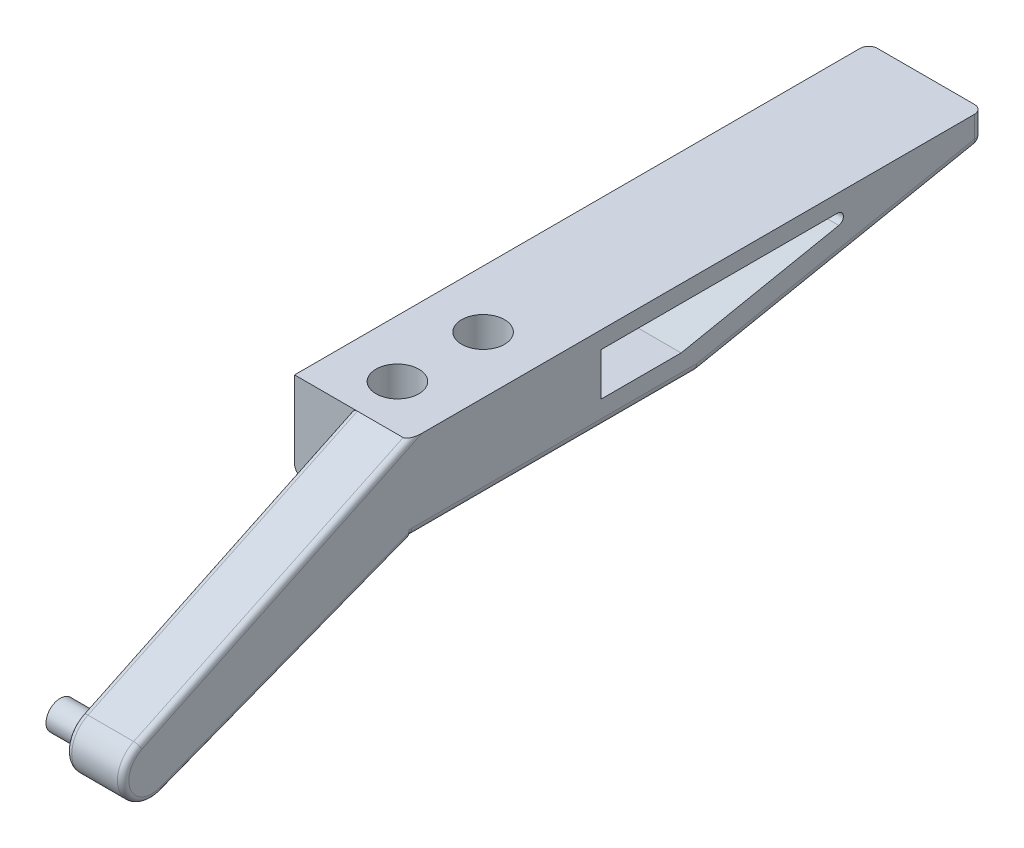
SolidWorks part; units mm, degrees
ref_plane "Front Plane" through (0, 0, 0) normal (0, 0, 1) x (1, 0, 0)
ref_plane "Top Plane" through (0, 0, 0) normal (0, 1, 0) x (1, 0, 0)
ref_plane "Right Plane" through (0, 0, 0) normal (1, 0, 0) x (0, 0, -1)
sketch "Sketch1" plane through (0, 0, 0) normal (0, 1, 0) x (1, 0, 0)
  line L1 (-20, 75) -> (20, 75)
  line L3 (-20, -75) -> (20, -75)
  line L4 (20, -75) -> (20, 75)
  line L5 (-20, -75) -> (-20, 75)
  circle A0 centre (0, -61.1649) radius 7.5
  circle A1 centre (0, -31.1649) radius 7.5
extrude "Boss-Extrude1" add sketch "Sketch1" against normal blind 30 contours L5 L1 L4 L3
sketch "Sketch3" plane through (0, 0, 0) normal (0, 1, 0) x (1, 0, 0)
  circle A0 centre (0, -60) radius 7.5
  circle A1 centre (0, -30) radius 7.5
extrude "Cut-Extrude1" cut sketch "Sketch3" against normal blind 30 contours A0 | A1
sketch "Sketch4" plane through (-20, 0, 0) normal (-1, 0, 0) x (0, 0, 1)
  line L1 (-75, -30) -> (-75, 0) construction
  line L2 (-75, -8) -> (0, -30)
  line L3 (75, -30) -> (-75, -30) construction
  line L4 (0, -30) -> (-75, -30)
  line L5 (-75, -30) -> (-75, -8)
extrude "Cut-Extrude2" cut sketch "Sketch4" against normal blind 49
sketch "Sketch6" plane through (0, 0, -75) normal (0, 0, -1) x (-1, 0, 0)
  line L1 (-20, 0) -> (20, 0)
  line L2 (-20, 0) -> (-20, -30)
  line L3 (-20, -30) -> (20, -30)
  line L4 (20, 0) -> (20, -30)
extrude "Boss-Extrude2" add sketch "Sketch6" along normal blind 50 and the other way blind 87
sketch "Sketch7" plane through (-20, 0, 0) normal (-1, 0, 0) x (0, 0, 1)
  line L1 (-125, -30) -> (-125, 0) construction
  line L2 (-125, -10) -> (-25, -30)
  line L3 (75, -30) -> (-125, -30) construction
  line L4 (-25, -30) -> (-125, -30)
  line L5 (-125, -30) -> (-125, -10)
extrude "Cut-Extrude3" cut sketch "Sketch7" against normal blind 50
sketch "Sketch8" plane through (0, 0, 75) normal (0, 0, 1) x (1, 0, 0)
  line L10 (20, -30) -> (6, -30)
  line L11 (-20, -30) -> (20, -30) construction
  line L12 (6, -30) -> (6, 0)
  line L13 (-20, 0) -> (20, 0) construction
  line L14 (6, 0) -> (20, 0)
  line L15 (20, 0) -> (20, -30)
  line L16 (-20, -30) -> (-6, -30)
  line L17 (-6, -30) -> (-6, 0)
  line L18 (-6, 0) -> (-20, 0)
  line L19 (-20, -30) -> (-20, 0) construction
  line L20 (-20, 0) -> (-20, -30)
extrude "Boss-Extrude4" add sketch "Sketch8" along normal blind 50
sketch "Sketch11" plane through (0, 0, 0) normal (0, 1, 0) x (1, 0, 0)
  line L0 (6, -75) -> (20, -75)
  line L1 (20, -125) -> (20, 125) construction
  line L2 (20, -75) -> (20, -125)
  line L3 (20, -125) -> (6, -125)
  line L4 (6, -125) -> (6, -75)
  line L5 (-6, -75) -> (-6, -125)
  line L6 (-6, -125) -> (-20, -125)
  line L7 (-20, -125) -> (-20, -75)
  line L8 (-20, -125) -> (-20, 125) construction
  line L9 (-20, -75) -> (-6, -75)
extrude "Cut-Extrude4" cut sketch "Sketch11" against normal blind 15
sketch "Sketch12" plane through (0, 0, 125) normal (0, 0, 1) x (1, 0, 0)
  line L1 (-20, -15) -> (-6, -15)
  line L2 (-20, -15) -> (-20, -30)
  line L3 (-20, -30) -> (-6, -30)
  line L4 (-6, -15) -> (-6, -30)
  line L5 (6, -15) -> (20, -15)
  line L6 (6, -15) -> (6, -30)
  line L7 (6, -30) -> (20, -30)
  line L8 (20, -15) -> (20, -30)
extrude "Boss-Extrude5" add sketch "Sketch12" along normal blind 10
sketch "Sketch13" plane through (-6, 0, 0) normal (1, 0, 0) x (0, 0, -1)
  circle A0 centre (-125, -22.5) radius 5
extrude "Boss-Extrude6" add sketch "Sketch13" along normal up to surface (12 mm away) contours A0 up to face at (6, -22.5, 105)
sketch "Sketch14" plane through (0, -30, 0) normal (0, -1, 0) x (1, 0, 0)
  circle A0 centre (0, 60) radius 7.5
  circle A1 centre (0, 60) radius 6
  circle A2 centre (0, 30) radius 6
  circle A3 centre (0, 30) radius 7.5
extrude "Boss-Extrude7" add sketch "Sketch14" against normal blind 5
sketch "Sketch15" plane through (20, 0, 0) normal (1, 0, 0) x (0, 0, -1)
  line L0 (125, 0) -> (105, 0)
  line L1 (-75, 0) -> (125, 0) construction
  circle A0 centre (52.5, 373.9316) radius 377.5991
extrude "Cut-Extrude5" cut sketch "Sketch15" against normal blind 50 contours A0
fillet "Fillet1" radius 3 2 edges at (20, -30, 55) (-20, -30, 55)
fillet "Fillet2" radius 3 8 edges at (-20, -18.5, -82.5) (-19.1213, -29.1213, -29.3934) (0, -30, -25) (19.1213, -29.1213, -29.3934) (-20, -5, -125) (20, -5, -125) (0, -10, -125) (20, -18.5, -82.5)
sketch "Sketch17" plane through (0, 0, 75) normal (0, 0, 1) x (1, 0, 0)
  line L0 (20, 0) -> (20, -30)
  line L1 (14.0365, -30) -> (20, -30)
  line L2 (6, -30) -> (17, -30) construction
  line L3 (20, 0) -> (-20, 0)
  line L4 (-20, 0) -> (-20, -30)
  line L5 (-20, -30) -> (14.0365, -30)
extrude "Boss-Extrude11" add sketch "Sketch17" along normal up to surface (60 mm away) up to face at (13.9243, -23.5243, 135)
sketch "Sketch23" plane through (0, 0, 135) normal (0, 0, 1) x (1, 0, 0)
  line L0 (-20, -15) -> (0, -15)
  line L1 (-20, 0) -> (-20, -30) construction
  line L3 (0, -30) -> (0, -15)
  line L4 (-20, -30) -> (20, -30) construction
  line L6 (-20, -30) -> (0, -30)
  line L7 (-20, -15) -> (-20, -30)
  line L9 (-20, -30) -> (20, -30)
  line L10 (-20, -30) -> (-20, 0)
  line L11 (-20, 0) -> (20, 0)
  line L12 (20, -30) -> (20, 0)
  line M1 (-20, 0) -> (-20, -30)
  line M2 (-20, -30) -> (20, -30)
  line M3 (20, -30) -> (20, 0)
  line M4 (20, 0) -> (-20, 0)
extrude "Cut-Extrude8" cut sketch "Sketch23" against normal up to surface (60 mm away) contours L3 L0 M2 M3 M4 M1 region at (3.3333, -12.5, 135) up to face at (19.2071, -29.2071, 75)
sketch "Sketch25" plane through (0, 0, 75) normal (0, 0, 1) x (1, 0, 0)
  line L0 (-20, -15) -> (-20, 0)
  line L1 (-20, 0) -> (0, 0)
  line L2 (-20, 0) -> (20, 0) construction
  line L3 (0, 0) -> (0, -15)
  line L4 (0, -15) -> (-20, -15)
extrude "Boss-Extrude13" add sketch "Sketch25" along normal up to surface (60 mm away) up to face at (-10, -22.5, 135)
sketch "Sketch26" plane through (0, 0, 0) normal (1, 0, 0) x (0, 0, -1)
  circle A0 centre (-125, -15) radius 5
extrude "Boss-Extrude14" add sketch "Sketch26" along normal up to surface (20 mm away) up to face at (20, -9.3154, -31.9576)
sketch "Sketch27" plane through (0, 0, 75) normal (0, 0, 1) x (1, 0, 0)
  line L1 (20, 0) -> (-20, 0)
  line L2 (20, 0) -> (20, -60)
  line L3 (20, -60) -> (-20, -60)
  line L4 (-20, 0) -> (-20, -60)
extrude "Boss-Extrude15" add sketch "Sketch27" along normal up to surface (60 mm away) up to face at (-10, -15, 135)
sketch "Sketch28" plane through (0, 0, 75) normal (0, 0, -1) x (-1, 0, 0)
  line L0 (20, -27) -> (20, -60) construction
  line L1 (-20, -60) -> (20, -60)
  line L2 (-20, -60) -> (-20, -30)
  line L3 (-20, -30) -> (20, -30)
  line L4 (20, -60) -> (20, -30)
extrude "Cut-Extrude9" cut sketch "Sketch28" against normal blind 1
sketch "Sketch29" plane through (0, 0, 135) normal (0, 0, 1) x (1, 0, 0)
  line L0 (20, 0) -> (-20, 0) construction
  line L1 (20, -60) -> (0, -60)
  line L2 (20, -60) -> (20, 0)
  line L3 (20, 0) -> (0, 0)
  line L4 (0, -60) -> (0, 0)
extrude "Cut-Extrude10" cut sketch "Sketch29" against normal up to surface (59 mm away) up to face at (0, -45, 76)
fillet "Fillet6" radius 3 1 edges at (-20, -30, 75.5)
fillet "Fillet7" radius 3 1 edges at (20, -30, 75.5)
sketch "Sketch30" plane through (0, 0, 135) normal (0, 0, 1) x (1, 0, 0)
  line L0 (-20, 0) -> (-20, -30)
  line L1 (-20, 0) -> (-20, -60) construction
  line L2 (-20, -15) -> (0, -15)
  line L3 (0, 0) -> (0, -60) construction
  line L4 (0, -15) -> (0, 0)
  line L5 (0, 0) -> (-20, 0)
  line M1 (0, -60) -> (0, 0)
  line M2 (0, 0) -> (-20, 0)
  line M3 (-20, 0) -> (-20, -60)
extrude "Cut-Extrude11" cut sketch "Sketch30" against normal up to surface (59 mm away) contours L2 M3 M1 M2 region at (-10, -7.5, 135) up to face at (11.5243, -17.5243, 76)
sketch "Sketch31" plane through (0, 0, 0) normal (1, 0, 0) x (0, 0, -1)
  line L0 (-129.7694, -41.2162) -> (-129.0122, -40.847)
  line L1 (-76, -15) -> (-76, -30)
  line L2 (-76, -30) -> (-118.7075, -57.7744)
  line L3 (-129.6113, -41.0081) -> (-129.7694, -41.2162)
  line L4 (-89.6197, -15) -> (-129.6113, -41.0081)
  line L5 (-76, -30) -> (-76, -60)
  line L6 (-76, -60) -> (-135, -60)
  line L7 (-135, -60) -> (-135, -15)
  line L8 (-135, -15) -> (-76, -15)
  line L9 (-96, -19.1494) -> (-129.6113, -41.0081) construction
  line L10 (-96, -15) -> (-96, -19.1494) construction
  circle A0 centre (-125.0122, -50.0122) radius 10
  line M9 (-76, -15) -> (-135, -15)
  line M10 (-135, -15) -> (-135, -60)
  line M11 (-135, -60) -> (-76, -60)
  line M12 (-76, -60) -> (-76, -30)
  dimension "D1" = 20
extrude "Cut-Extrude13" cut sketch "Sketch31" against normal blind 28 contours A0 M10 M11 | A0 L2 M11 M12 | A0 L3 L4 M9 M10 region at (0, -24.9817, 119.9741) region at (0, -57.7806, 132.7806) region at (0, -50.0084, 91.4032)
sketch "Sketch32" plane through (0, 0, 0) normal (1, 0, 0) x (0, 0, -1)
  line L0 (-76, -30) -> (-76, 0)
  line L1 (-76, 0) -> (-129.7694, -41.2162)
  line L2 (-129.7694, -41.2162) -> (-76, -30)
extrude "Boss-Extrude16" add sketch "Sketch32" against normal up to surface (20 mm away) up to face at (-20, -28.5466, 55.3206)
sketch "Sketch33" plane through (0, 0, 0) normal (1, 0, 0) x (0, 0, -1)
  circle A0 centre (-125.0122, -50.0122) radius 5
extrude "Boss-Extrude17" add sketch "Sketch33" along normal up to surface (20 mm away) contours A0 up to face at (20, -11.526, -18.3379)
ref_plane "Plane2" through (0, 10, 0) normal (0, 1, 0) x (1, 0, 0)
sketch "Sketch34" plane through (0, 0, 0) normal (1, 0, 0) x (0, 0, -1)
  line L0 (-129.6113, -41.0081) -> (-129.7694, -41.2162)
  line L1 (-129.6113, -41.0081) -> (-76, 0)
  line L2 (-76, 0) -> (-76, -30)
  line L3 (-76, -30) -> (-76, 0) construction
  line L4 (-76, -30) -> (-118.7075, -57.7744)
  arc A0 (-129.7694, -41.2162) -> (-118.7075, -57.7744) centre (-125.0122, -50.0122) ccw
extrude "Cut-Extrude15" cut sketch "Sketch34" against normal up to surface (20 mm away) up to face at (-20, -30.8448, 56.4126)
extrude "Cut-Extrude16" cut sketch "Sketch34<2>" along normal up to surface (20 mm away) up to face at (20, -11.526, -18.3379)
sketch "Sketch34<2>" plane through (0, 0, 0) normal (1, 0, 0) x (0, 0, -1) same geometry as "Sketch34"
extrude "Boss-Extrude19" add sketch "Sketch34<3>" along normal up to surface (20 mm away) up to face at (20, -11.526, -18.3379)
sketch "Sketch34<3>" plane through (0, 0, 0) normal (1, 0, 0) x (0, 0, -1) same geometry as "Sketch34"
sketch "Sketch38" plane through (0, 0, 0) normal (-1, 0, 0) x (0, 0, 1)
  circle A0 centre (125.0122, -50.0122) radius 5
sketch "Sketch39" plane through (0, 0, 0) normal (-1, 0, 0) x (0, 0, 1)
  line L0 (162.0273, -59.1835) -> (76, -78.9424)
  line L1 (169.997, -40.8408) -> (76, 0)
  line L2 (76, -30) -> (76, 0) construction
  line L3 (76, 0) -> (129.6113, -41.0081) construction
  line L4 (76, 0) -> (76, -30)
  line L6 (162.0273, -59.1835) -> (76, -30)
  line L7 (76, -78.9424) -> (76, -30)
  arc A0 (162.0273, -59.1835) -> (169.997, -40.8408) centre (166.0122, -50.0122) ccw
  line M6 (129.6113, -41.0081) -> (76, 0)
  line M8 (76, -30) -> (118.7075, -57.7744)
  arc M9 (118.7075, -57.7744) -> (129.7694, -41.2162) centre (125.0122, -50.0122) ccw
  line M10 (129.7694, -41.2162) -> (129.6113, -41.0081)
extrude "Cut-Extrude17" cut sketch "Sketch39" against normal blind 23 contours L7 L0 L6 M9 M8 | L6 M9 M8 region at (0, -58.461, 102.3812) region at (0, -47.5284, 112.7515)
extrude "Boss-Extrude21" add sketch "Sketch39<3>" against normal blind 20 contours L6 A0 L1 M6 M10 M9 region at (0, -36.3816, 138.4753)
sketch "Sketch39<3>" plane through (0, 0, 0) normal (-1, 0, 0) x (0, 0, 1) same geometry as "Sketch39"
sketch "Sketch40" plane through (0, -4.0074, 0) normal (-1, 0, 0) x (0, 0, 1)
  circle A0 centre (166.0122, -50.0122) radius 4.5
extrude "Boss-Extrude22" add sketch "Sketch40" along normal up to surface (12 mm away)
ref_plane "Plane5" through (0, 0, 0) normal (-1, 0, 0) x (0, 0, 1)
sketch "Sketch42" plane through (0, 0, 0) normal (-1, 0, 0) x (0, 0, 1)
  line L0 (166.0122, -54.0196) -> (166.0122, -54.0122)
  line L1 (170.3172, -44.9863) -> (76, 0)
  line L2 (76, 0) -> (76, -30)
  line L3 (162.4124, -63.3418) -> (76, -30)
  line L4 (175.8593, -55.7544) -> (179.2704, -36.4741)
  line L5 (179.2704, -36.4741) -> (76, 0)
  circle A0 centre (166.0122, -54.0122) radius 10
extrude "Cut-Extrude18" cut sketch "Sketch42" against normal blind 20 contours A0 L4 L5 L1 region at (0, -28.5967, 144.6768)
extrude "Boss-Extrude23" add sketch "Sketch42<4>" against normal blind 20 contours A0 L1 L2 L3 | A0 region at (0, -31.8969, 115.5317) region at (0, -48.8269, 174.2302)
sketch "Sketch42<4>" plane through (0, 0, 0) normal (-1, 0, 0) x (0, 0, 1) same geometry as "Sketch42"
sketch "Sketch43" plane through (0, 0, 0) normal (-1, 0, 0) x (0, 0, 1)
  circle A0 centre (166.0122, -54.0196) radius 5.5
extrude "Boss-Extrude24" add sketch "Sketch43" along normal blind 2
fillet "Fillet8" radius 2 6 edges at (20, -46.6709, 119.2062) (20, -57.9675, 175.1967) (0, -46.6709, 119.2062) (0, -57.9675, 175.1967) (20, -22.4932, 123.1586) (0, -22.4932, 123.1586)
sketch "Sketch44" plane through (20, 0, 0) normal (1, 0, 0) x (0, 0, -1)
  line L0 (0, 0) -> (105, 0)
  line L1 (105, 0) -> (105, -4.5055)
  line L2 (105, -4.5055) -> (0, -4.5055)
  line L3 (0, -4.5055) -> (0, 0)
extrude "Boss-Extrude25" add sketch "Sketch44" against normal up to surface (40 mm away) up to face at (-20, -11.526, -18.3379)
sketch "Sketch46" plane through (20, 0, 0) normal (1, 0, 0) x (0, 0, -1)
  line L0 (-71.3543, 0) -> (122, 0) construction
  line L1 (25.3229, 0) -> (-14.6771, 0)
  line L2 (25.3229, 0) -> (25.3229, -6)
  line L3 (25.3229, -27) -> (-14.6771, -27)
  line L4 (-14.6771, 0) -> (-14.6771, -27)
  line L5 (-75, -27) -> (24.7029, -27) construction
  line L6 (63.8734, -19.1659) -> (62.5127, -12.362)
  line L7 (24.7029, -27) -> (122, -7.5406) construction
  line L8 (19.3229, -6) -> (-8.6771, -6)
  line L9 (-8.6771, -6) -> (-8.6771, -21)
  line L10 (19.3229, -21) -> (-8.6771, -21)
  line L12 (19.3229, -21) -> (94.3229, -6)
  line L13 (19.3229, -6) -> (103.4664, -6)
  line L14 (25.3229, -19.8) -> (25.3229, -27)
  line L15 (19.3229, -6) -> (19.3229, -21) construction
  line L16 (25.3229, 0) -> (25.3229, -27) construction
  dimension "D1" = 6
extrude "Cut-Extrude20" cut sketch "Sketch46" against normal blind 59 and the other way through all contours L13 L8 L9 L10 L12 region at (20, -12.0687, -27.6511)
fillet "Fillet10" radius 2 1 edges at (0, -6, -94.3229)
sketch "Sketch47" plane through (-12, 0, 0) normal (-1, 0, 0) x (0, 0, 1)
  circle A0 centre (166.0122, -54.0196) radius 5
extrude "Boss-Extrude26" add sketch "Sketch47" against normal up to surface (10 mm away) up to face at (-2, -54.0196, 170.5122)
